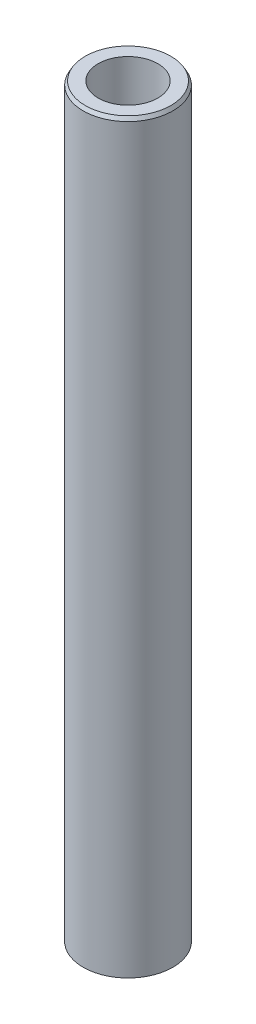
SolidWorks part; units mm, degrees
ref_plane "Front Plane" through (0, 0, 0) normal (0, 0, 1) x (1, 0, 0)
ref_plane "Top Plane" through (0, 0, 0) normal (0, 1, 0) x (1, 0, 0)
ref_plane "Right Plane" through (0, 0, 0) normal (1, 0, 0) x (0, 0, -1)
sketch "Sketch1" plane through (0, 0, 0) normal (0, 1, 0) x (1, 0, 0)
  circle A0 centre (0, 0) radius 30
  dimension "SHAFT_OD" = 60
extrude "Boss-Extrude1" add sketch "Sketch1" along normal blind 499.9814
sketch "Sketch2" plane through (0, 0, 0) normal (0, 1, 0) x (1, 0, 0)
  circle A0 centre (0, 0) radius 19.9571
  dimension "BORE_D" = 39.9142
extrude "Cut-Extrude1" cut sketch "Sketch2" along normal through all
chamfer "Chamfer1" distance 2.4014 angle 30 2 edges at (0, 499.9814, 30) (0, 0, 30) first distance on face at (0, 499.9814, 30) first distance on face at (0, 0, 19.9571)
